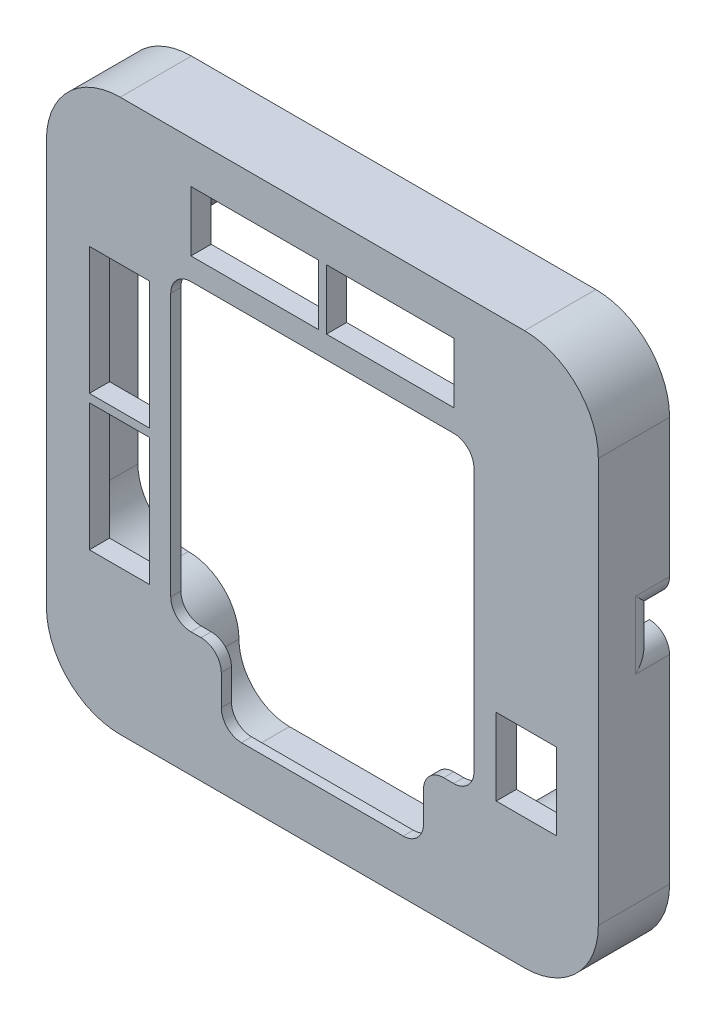
SolidWorks part; units mm, degrees
ref_plane "Front Plane" through (0, 0, 0) normal (0, 0, 1) x (1, 0, 0)
ref_plane "Top Plane" through (0, 0, 0) normal (0, 1, 0) x (1, 0, 0)
ref_plane "Right Plane" through (0, 0, 0) normal (1, 0, 0) x (0, 0, -1)
sketch "Front_Sketch" plane through (0, 0, 0) normal (0, 0, 1) x (1, 0, 0)
  line L0 (-5, 0) -> (-45, 0) construction
  line L1 (0, 45) -> (0, 5) construction
  line L2 (-45, 50) -> (-5, 50) construction
  line L3 (-50, 5) -> (-50, 45) construction
  line L4 (-47.95, 12.1) -> (-44.05, 12.1) construction
  line L5 (-43.55, 12.1) -> (-44.05, 12.1) construction
  line L6 (-43.05, 12.1) -> (-43.55, 12.1) construction
  line L7 (-43.05, 12.1) -> (-42.2, 12.1) construction
  line L8 (-42.2, 12.1) -> (-42.2, 14.05) construction
  line L9 (-42.2, 14.8) -> (-42.2, 14.05) construction
  line L10 (-42.2, 15.55) -> (-42.2, 14.8) construction
  line L11 (-42.2, 15.55) -> (-42.2, 21.05) construction
  line L12 (-42.2, 21.05) -> (-42.2, 21.8) construction
  line L13 (-42.2, 21.8) -> (-42.2, 22.55) construction
  line L14 (-42.2, 22.55) -> (-42.2, 24.5) construction
  line L15 (-42.2, 24.5) -> (-43.05, 24.5) construction
  line L16 (-43.55, 24.5) -> (-43.05, 24.5) construction
  line L17 (-43.55, 24.5) -> (-44.05, 24.5) construction
  line L18 (-47.95, 24.5) -> (-47.95, 12.1) construction
  line L19 (-44.05, 24.5) -> (-47.95, 24.5) construction
  line L20 (-47.95, 25.5) -> (-44.05, 25.5) construction
  line L21 (-43.55, 25.5) -> (-44.05, 25.5) construction
  line L22 (-43.05, 25.5) -> (-43.55, 25.5) construction
  line L23 (-43.05, 25.5) -> (-42.2, 25.5) construction
  line L24 (-42.2, 25.5) -> (-42.2, 27.45) construction
  line L25 (-42.2, 28.2) -> (-42.2, 27.45) construction
  line L26 (-42.2, 27.7) -> (-42.2, 27.45) construction
  line L27 (-42.2, 28.95) -> (-42.2, 28.2) construction
  line L28 (-42.2, 28.95) -> (-42.2, 34.45) construction
  line L29 (-42.2, 34.45) -> (-42.2, 35.2) construction
  line L30 (-42.2, 35.2) -> (-42.2, 35.95) construction
  line L31 (-42.2, 35.7) -> (-42.2, 35.95) construction
  line L32 (-42.2, 35.95) -> (-42.2, 37.9) construction
  line L33 (-42.2, 37.9) -> (-43.05, 37.9) construction
  line L34 (-43.55, 37.9) -> (-43.05, 37.9) construction
  line L35 (-43.55, 37.9) -> (-44.05, 37.9) construction
  line L36 (-44.05, 37.9) -> (-47.95, 37.9) construction
  line L37 (-47.95, 37.9) -> (-47.95, 25.5) construction
  line L38 (-34.45, 42.3) -> (-35.2, 42.3) construction
  line L39 (-35.2, 42.3) -> (-35.95, 42.3) construction
  line L40 (-35.7, 42.3) -> (-35.95, 42.3) construction
  line L41 (-37.9, 42.3) -> (-35.95, 42.3) construction
  line L42 (-37.9, 43.15) -> (-37.9, 42.3) construction
  line L43 (-37.9, 43.15) -> (-37.9, 43.65) construction
  line L44 (-37.9, 43.65) -> (-37.9, 44.15) construction
  line L45 (-34.45, 42.3) -> (-28.95, 42.3) construction
  line L46 (-28.95, 42.3) -> (-28.2, 42.3) construction
  line L47 (-28.2, 42.3) -> (-27.45, 42.3) construction
  line L48 (-27.7, 42.3) -> (-27.45, 42.3) construction
  line L49 (-27.45, 42.3) -> (-25.5, 42.3) construction
  line L50 (-25.5, 42.3) -> (-25.5, 43.15) construction
  line L51 (-25.5, 43.65) -> (-25.5, 43.15) construction
  line L52 (-25.5, 43.65) -> (-25.5, 44.15) construction
  line L53 (-25.5, 44.15) -> (-25.5, 48.05) construction
  line L54 (-25.5, 48.05) -> (-37.9, 48.05) construction
  line L55 (-37.9, 48.05) -> (-37.9, 44.15) construction
  line L56 (-24.5, 43.65) -> (-24.5, 44.15) construction
  line L57 (-24.5, 43.15) -> (-24.5, 43.65) construction
  line L58 (-24.5, 43.15) -> (-24.5, 42.3) construction
  line L59 (-24.5, 42.3) -> (-22.55, 42.3) construction
  line L60 (-21.8, 42.3) -> (-22.55, 42.3) construction
  line L61 (-21.05, 42.3) -> (-21.8, 42.3) construction
  line L62 (-21.05, 42.3) -> (-15.55, 42.3) construction
  line L63 (-15.55, 42.3) -> (-14.8, 42.3) construction
  line L64 (-14.8, 42.3) -> (-14.05, 42.3) construction
  line L65 (-14.3, 42.3) -> (-14.05, 42.3) construction
  line L66 (-14.05, 42.3) -> (-12.1, 42.3) construction
  line L67 (-12.1, 42.3) -> (-12.1, 43.15) construction
  line L68 (-12.1, 43.65) -> (-12.1, 43.15) construction
  line L69 (-12.1, 43.65) -> (-12.1, 44.15) construction
  line L70 (-12.1, 44.15) -> (-12.1, 48.05) construction
  line L71 (-12.1, 48.05) -> (-24.5, 48.05) construction
  line L72 (-24.5, 48.05) -> (-24.5, 44.15) construction
  line L73 (-6.35, 10.7) -> (-5.85, 10.7) construction
  line L74 (-6.35, 10.7) -> (-6.85, 10.7) construction
  line L75 (-7.7, 10.7) -> (-6.85, 10.7) construction
  line L76 (-7.7, 12.65) -> (-7.7, 10.7) construction
  line L77 (-7.7, 13.4) -> (-7.7, 12.65) construction
  line L78 (-7.7, 13.4) -> (-7.7, 15.4) construction
  line L79 (-7.7, 15.4) -> (-7.7, 16.15) construction
  line L80 (-7.7, 15.9) -> (-7.7, 16.15) construction
  line L81 (-7.7, 18.1) -> (-7.7, 16.15) construction
  line L82 (-6.85, 18.1) -> (-7.7, 18.1) construction
  line L83 (-6.85, 18.1) -> (-6.35, 18.1) construction
  line L84 (-6.35, 18.1) -> (-5.85, 18.1) construction
  line L85 (-1.95, 18.1) -> (-5.85, 18.1) construction
  line L86 (-1.95, 10.7) -> (-1.95, 18.1) construction
  line L87 (-5.85, 10.7) -> (-1.95, 10.7) construction
  line L88 (0.6, 26.77) -> (-0.4, 26.77) construction
  line L89 (0.6, 26.77) -> (0.8, 26.97) construction
  line L90 (0.8, 26.97) -> (0.8, 27.87) construction
  line L91 (0.8, 27.87) -> (0.6, 28.07) construction
  line L92 (0.6, 28.07) -> (-0.4, 28.07) construction
  line L93 (-5, 0) -> (-45, 0)
  line L94 (0, 45) -> (0, 5)
  line L95 (-45, 50) -> (-5, 50)
  line L96 (-50, 5) -> (-50, 45)
  line L97 (-47.95, 12.1) -> (-44.05, 12.1)
  line L98 (-43.55, 12.1) -> (-44.05, 12.1)
  line L99 (-43.05, 12.1) -> (-43.55, 12.1)
  line L100 (-43.05, 12.1) -> (-42.2, 12.1)
  line L101 (-42.2, 12.1) -> (-42.2, 14.05)
  line L102 (-42.2, 14.8) -> (-42.2, 14.05)
  line L103 (-42.2, 15.55) -> (-42.2, 14.8)
  line L104 (-42.2, 15.55) -> (-42.2, 21.05)
  line L105 (-42.2, 21.05) -> (-42.2, 21.8)
  line L106 (-42.2, 21.8) -> (-42.2, 22.55)
  line L107 (-42.2, 22.55) -> (-42.2, 24.5)
  line L108 (-42.2, 24.5) -> (-43.05, 24.5)
  line L109 (-43.55, 24.5) -> (-43.05, 24.5)
  line L110 (-43.55, 24.5) -> (-44.05, 24.5)
  line L111 (-47.95, 24.5) -> (-47.95, 12.1)
  line L112 (-44.05, 24.5) -> (-47.95, 24.5)
  line L113 (-47.95, 25.5) -> (-44.05, 25.5)
  line L114 (-43.55, 25.5) -> (-44.05, 25.5)
  line L115 (-43.05, 25.5) -> (-43.55, 25.5)
  line L116 (-43.05, 25.5) -> (-42.2, 25.5)
  line L117 (-42.2, 25.5) -> (-42.2, 27.45)
  line L118 (-42.2, 28.2) -> (-42.2, 27.45)
  line L119 (-42.2, 27.7) -> (-42.2, 27.45)
  line L120 (-42.2, 28.95) -> (-42.2, 28.2)
  line L121 (-42.2, 28.95) -> (-42.2, 34.45)
  line L122 (-42.2, 34.45) -> (-42.2, 35.2)
  line L123 (-42.2, 35.2) -> (-42.2, 35.95)
  line L124 (-42.2, 35.7) -> (-42.2, 35.95)
  line L125 (-42.2, 35.95) -> (-42.2, 37.9)
  line L126 (-42.2, 37.9) -> (-43.05, 37.9)
  line L127 (-43.55, 37.9) -> (-43.05, 37.9)
  line L128 (-43.55, 37.9) -> (-44.05, 37.9)
  line L129 (-44.05, 37.9) -> (-47.95, 37.9)
  line L130 (-47.95, 37.9) -> (-47.95, 25.5)
  line L131 (-34.45, 42.3) -> (-35.2, 42.3)
  line L132 (-35.2, 42.3) -> (-35.95, 42.3)
  line L133 (-35.7, 42.3) -> (-35.95, 42.3)
  line L134 (-37.9, 42.3) -> (-35.95, 42.3)
  line L135 (-37.9, 43.15) -> (-37.9, 42.3)
  line L136 (-37.9, 43.15) -> (-37.9, 43.65)
  line L137 (-37.9, 43.65) -> (-37.9, 44.15)
  line L138 (-34.45, 42.3) -> (-28.95, 42.3)
  line L139 (-28.95, 42.3) -> (-28.2, 42.3)
  line L140 (-28.2, 42.3) -> (-27.45, 42.3)
  line L141 (-27.7, 42.3) -> (-27.45, 42.3)
  line L142 (-27.45, 42.3) -> (-25.5, 42.3)
  line L143 (-25.5, 42.3) -> (-25.5, 43.15)
  line L144 (-25.5, 43.65) -> (-25.5, 43.15)
  line L145 (-25.5, 43.65) -> (-25.5, 44.15)
  line L146 (-25.5, 44.15) -> (-25.5, 48.05)
  line L147 (-25.5, 48.05) -> (-37.9, 48.05)
  line L148 (-37.9, 48.05) -> (-37.9, 44.15)
  line L149 (-24.5, 43.65) -> (-24.5, 44.15)
  line L150 (-24.5, 43.15) -> (-24.5, 43.65)
  line L151 (-24.5, 43.15) -> (-24.5, 42.3)
  line L152 (-24.5, 42.3) -> (-22.55, 42.3)
  line L153 (-21.8, 42.3) -> (-22.55, 42.3)
  line L154 (-21.05, 42.3) -> (-21.8, 42.3)
  line L155 (-21.05, 42.3) -> (-15.55, 42.3)
  line L156 (-15.55, 42.3) -> (-14.8, 42.3)
  line L157 (-14.8, 42.3) -> (-14.05, 42.3)
  line L158 (-14.3, 42.3) -> (-14.05, 42.3)
  line L159 (-14.05, 42.3) -> (-12.1, 42.3)
  line L160 (-12.1, 42.3) -> (-12.1, 43.15)
  line L161 (-12.1, 43.65) -> (-12.1, 43.15)
  line L162 (-12.1, 43.65) -> (-12.1, 44.15)
  line L163 (-12.1, 44.15) -> (-12.1, 48.05)
  line L164 (-12.1, 48.05) -> (-24.5, 48.05)
  line L165 (-24.5, 48.05) -> (-24.5, 44.15)
  line L166 (-6.35, 10.7) -> (-5.85, 10.7)
  line L167 (-6.35, 10.7) -> (-6.85, 10.7)
  line L168 (-7.7, 10.7) -> (-6.85, 10.7)
  line L169 (-7.7, 12.65) -> (-7.7, 10.7)
  line L170 (-7.7, 13.4) -> (-7.7, 12.65)
  line L171 (-7.7, 13.4) -> (-7.7, 15.4)
  line L172 (-7.7, 15.4) -> (-7.7, 16.15)
  line L173 (-7.7, 15.9) -> (-7.7, 16.15)
  line L174 (-7.7, 18.1) -> (-7.7, 16.15)
  line L175 (-6.85, 18.1) -> (-7.7, 18.1)
  line L176 (-6.85, 18.1) -> (-6.35, 18.1)
  line L177 (-6.35, 18.1) -> (-5.85, 18.1)
  line L178 (-1.95, 18.1) -> (-5.85, 18.1)
  line L179 (-1.95, 10.7) -> (-1.95, 18.1)
  line L180 (-5.85, 10.7) -> (-1.95, 10.7)
  line L181 (0.6, 26.77) -> (-0.4, 26.77)
  line L182 (0.6, 26.77) -> (0.8, 26.97)
  line L183 (0.8, 26.97) -> (0.8, 27.87)
  line L184 (0.8, 27.87) -> (0.6, 28.07)
  line L185 (0.6, 28.07) -> (-0.4, 28.07)
  arc A0 (-5, 0) -> (0, 5) centre (-5, 5) ccw construction
  arc A1 (-50, 5) -> (-45, 0) centre (-45, 5) ccw construction
  arc A2 (0, 45) -> (-5, 50) centre (-5, 45) ccw construction
  arc A3 (-45, 50) -> (-50, 45) centre (-45, 45) ccw construction
  circle A4 centre (-5, 5) radius 2.15 construction
  circle A5 centre (-45, 5) radius 2.15 construction
  circle A6 centre (-45, 45) radius 2.15 construction
  circle A7 centre (-5, 45) radius 2.15 construction
  arc A8 (-5, 0) -> (0, 5) centre (-5, 5) ccw
  arc A9 (-50, 5) -> (-45, 0) centre (-45, 5) ccw
  arc A10 (0, 45) -> (-5, 50) centre (-5, 45) ccw
  arc A11 (-45, 50) -> (-50, 45) centre (-45, 45) ccw
  circle A12 centre (-5, 5) radius 2.15
  circle A13 centre (-45, 5) radius 2.15
  circle A14 centre (-45, 45) radius 2.15
  circle A15 centre (-5, 45) radius 2.15
sketch "Top_Sketch" plane through (0, 0, 0) normal (0, 1, 0) x (1, 0, 0)
  line L0 (-12.1, -1.64) -> (-12.1, -8.64) construction
  line L1 (-24.5, -1.64) -> (-24.5, -8.64) construction
  line L2 (-12.1, -8.64) -> (-24.5, -8.64) construction
  line L3 (-25.5, -8.64) -> (-37.9, -8.64) construction
  line L4 (-25.5, -1.64) -> (-25.5, -8.64) construction
  line L5 (-37.9, -1.64) -> (-37.9, -8.64) construction
  line L6 (-42.2, -1.64) -> (-42.2, -8.64) construction
  line L7 (-43.05, -8.64) -> (-42.2, -8.64) construction
  line L8 (-47.95, -8.64) -> (-44.05, -8.64) construction
  line L9 (-47.95, -1.64) -> (-47.95, -8.64) construction
  line L10 (-7.7, -1.64) -> (-7.7, -8.64) construction
  line L11 (-7.7, -8.64) -> (-6.85, -8.64) construction
  line L12 (-5.85, -8.64) -> (-1.95, -8.64) construction
  line L13 (-1.95, -1.64) -> (-1.95, -8.64) construction
  line L14 (0.6, -2.84) -> (-0.4, -2.84) construction
  line L15 (0.6, -2.84) -> (0.8, -2.84) construction
  line L16 (0.8, -2.04) -> (0.8, -2.84) construction
  line L17 (0.6, -2.04) -> (0.8, -2.04) construction
  line L18 (0.6, -2.04) -> (-0.5, -2.04) construction
  line L19 (-5, -1.59) -> (0, -1.59) construction
  line L20 (0, 0) -> (0, -1.59) construction
  line L21 (-5, 0) -> (0, 0) construction
  line L22 (-5, -1.59) -> (-45, -1.59) construction
  line L23 (-45, 0) -> (-5, 0) construction
  line L24 (-50, -1.59) -> (-45, -1.59) construction
  line L25 (-50, 0) -> (-45, 0) construction
  line L26 (-50, 0) -> (-50, -1.59) construction
  line L27 (-12.1, -1.64) -> (-12.1, -8.64)
  line L28 (-24.5, -1.64) -> (-24.5, -8.64)
  line L29 (-12.1, -8.64) -> (-24.5, -8.64)
  line L30 (-25.5, -8.64) -> (-37.9, -8.64)
  line L31 (-25.5, -1.64) -> (-25.5, -8.64)
  line L32 (-37.9, -1.64) -> (-37.9, -8.64)
  line L33 (-42.2, -1.64) -> (-42.2, -8.64)
  line L34 (-43.05, -8.64) -> (-42.2, -8.64)
  line L35 (-47.95, -8.64) -> (-44.05, -8.64)
  line L36 (-47.95, -1.64) -> (-47.95, -8.64)
  line L37 (-7.7, -1.64) -> (-7.7, -8.64)
  line L38 (-7.7, -8.64) -> (-6.85, -8.64)
  line L39 (-5.85, -8.64) -> (-1.95, -8.64)
  line L40 (-1.95, -1.64) -> (-1.95, -8.64)
  line L41 (0.6, -2.84) -> (-0.4, -2.84)
  line L42 (0.6, -2.84) -> (0.8, -2.84)
  line L43 (0.8, -2.04) -> (0.8, -2.84)
  line L44 (0.6, -2.04) -> (0.8, -2.04)
  line L45 (0.6, -2.04) -> (-0.5, -2.04)
  line L46 (-5, -1.59) -> (0, -1.59)
  line L47 (0, 0) -> (0, -1.59)
  line L48 (-5, 0) -> (0, 0)
  line L49 (-5, -1.59) -> (-45, -1.59)
  line L50 (-45, 0) -> (-5, 0)
  line L51 (-50, -1.59) -> (-45, -1.59)
  line L52 (-50, 0) -> (-45, 0)
  line L53 (-50, 0) -> (-50, -1.59)
  point P4 (0, 0)
  point P5 (0, 0)
  point P9 (0, 0)
  point P11 (0, 0)
sketch "Right_Sketch" plane through (0, 0, 0) normal (1, 0, 0) x (0, 0, -1)
  line L0 (-1.64, 10.7) -> (-8.64, 10.7) construction
  line L1 (-8.64, 10.7) -> (-8.64, 18.1) construction
  line L2 (-8.64, 23.85) -> (-8.64, 12.75) construction
  line L3 (-8.64, 22.55) -> (-8.64, 24.5) construction
  line L4 (-1.64, 24.5) -> (-8.64, 24.5) construction
  line L5 (-1.64, 25.5) -> (-8.64, 25.5) construction
  line L6 (-8.64, 37.25) -> (-8.64, 26.15) construction
  line L7 (-8.64, 25.5) -> (-8.64, 27.45) construction
  line L8 (-8.64, 28.95) -> (-8.64, 34.45) construction
  line L9 (-8.64, 35.95) -> (-8.64, 37.9) construction
  line L10 (-1.64, 37.9) -> (-8.64, 37.9) construction
  line L11 (-8.64, 42.3) -> (-8.64, 43.15) construction
  line L12 (-1.64, 48.05) -> (-8.64, 48.05) construction
  line L13 (-8.64, 44.15) -> (-8.64, 48.05) construction
  line L14 (-1.64, 42.3) -> (-8.64, 42.3) construction
  line L15 (-2.44, 29.25) -> (-2.84, 29.25) construction
  line L16 (-2.04, 28.07) -> (-2.84, 28.07) construction
  line L17 (-2.84, 27.87) -> (-2.84, 28.07) construction
  line L18 (-2.84, 26.97) -> (-2.84, 27.87) construction
  line L19 (-2.84, 26.77) -> (-2.84, 26.97) construction
  line L20 (-2.04, 26.97) -> (-2.04, 27.87) construction
  line L21 (-2.04, 26.77) -> (-2.04, 26.97) construction
  line L22 (-2.04, 26.77) -> (-2.84, 26.77) construction
  line L23 (0, 50) -> (-1.59, 50) construction
  line L24 (0, 45) -> (0, 50) construction
  line L25 (-1.59, 50) -> (-1.59, 45) construction
  line L26 (0, 5) -> (0, 45) construction
  line L27 (-1.59, 45) -> (-1.59, 5) construction
  line L28 (0, 5) -> (0, 0) construction
  line L29 (-1.59, 5) -> (-1.59, 0) construction
  line L30 (0, 0) -> (-1.59, 0) construction
  line L31 (-1.64, 10.7) -> (-8.64, 10.7)
  line L32 (-8.64, 10.7) -> (-8.64, 18.1)
  line L33 (-8.64, 23.85) -> (-8.64, 12.75)
  line L34 (-8.64, 22.55) -> (-8.64, 24.5)
  line L35 (-1.64, 24.5) -> (-8.64, 24.5)
  line L36 (-1.64, 25.5) -> (-8.64, 25.5)
  line L37 (-8.64, 37.25) -> (-8.64, 26.15)
  line L38 (-8.64, 25.5) -> (-8.64, 27.45)
  line L39 (-8.64, 28.95) -> (-8.64, 34.45)
  line L40 (-8.64, 35.95) -> (-8.64, 37.9)
  line L41 (-1.64, 37.9) -> (-8.64, 37.9)
  line L42 (-8.64, 42.3) -> (-8.64, 43.15)
  line L43 (-1.64, 48.05) -> (-8.64, 48.05)
  line L44 (-8.64, 44.15) -> (-8.64, 48.05)
  line L45 (-1.64, 42.3) -> (-8.64, 42.3)
  line L46 (-2.44, 29.25) -> (-2.84, 29.25)
  line L47 (-2.04, 28.07) -> (-2.84, 28.07)
  line L48 (-2.84, 27.87) -> (-2.84, 28.07)
  line L49 (-2.84, 26.97) -> (-2.84, 27.87)
  line L50 (-2.84, 26.77) -> (-2.84, 26.97)
  line L51 (-2.04, 26.97) -> (-2.04, 27.87)
  line L52 (-2.04, 26.77) -> (-2.04, 26.97)
  line L53 (-2.04, 26.77) -> (-2.84, 26.77)
  line L54 (0, 50) -> (-1.59, 50)
  line L55 (0, 45) -> (0, 50)
  line L56 (-1.59, 50) -> (-1.59, 45)
  line L57 (0, 5) -> (0, 45)
  line L58 (-1.59, 45) -> (-1.59, 5)
  line L59 (0, 5) -> (0, 0)
  line L60 (-1.59, 5) -> (-1.59, 0)
  line L61 (0, 0) -> (-1.59, 0)
sketch "Wall_Sketch" plane through (0, 0, 0) normal (0, 0, 1) x (1, 0, 0)
  line L4 (-52.3, 45) -> (-52.3, 5)
  line L5 (-45, -2.3) -> (-5, -2.3)
  line L6 (2.3, 5) -> (2.3, 45)
  line L7 (-5, 52.3) -> (-45, 52.3)
  line L8 (-5, 50.3) -> (-45, 50.3)
  line L9 (0.3, 5) -> (0.3, 45)
  line L10 (-45, -0.3) -> (-5, -0.3)
  line L11 (-50.3, 45) -> (-50.3, 5)
  line L12 (-5, 50.3) -> (-45, 50.3)
  line L13 (0.3, 5) -> (0.3, 45)
  line L14 (-45, -0.3) -> (-5, -0.3)
  line L15 (-50.3, 45) -> (-50.3, 5)
  arc A4 (-45, 52.3) -> (-52.3, 45) centre (-45, 45) ccw
  arc A5 (-52.3, 5) -> (-45, -2.3) centre (-45, 5) ccw
  arc A6 (-5, -2.3) -> (2.3, 5) centre (-5, 5) ccw
  arc A7 (2.3, 45) -> (-5, 52.3) centre (-5, 45) ccw
  arc A8 (0.3, 45) -> (-5, 50.3) centre (-5, 45) ccw
  arc A9 (-5, -0.3) -> (0.3, 5) centre (-5, 5) ccw
  arc A10 (-50.3, 5) -> (-45, -0.3) centre (-45, 5) ccw
  arc A11 (-45, 50.3) -> (-50.3, 45) centre (-45, 45) ccw
  arc A12 (0.3, 45) -> (-5, 50.3) centre (-5, 45) ccw
  arc A13 (-5, -0.3) -> (0.3, 5) centre (-5, 5) ccw
  arc A14 (-50.3, 5) -> (-45, -0.3) centre (-45, 5) ccw
  arc A15 (-45, 50.3) -> (-50.3, 45) centre (-45, 45) ccw
  dimension "D1" = 0.3
  dimension "D2" = 2
extrude "Wall_Extrude_Boss" add sketch "Wall_Sketch" against normal up to vertex (-1.59 mm away) from vertex up to point (-50, 0, 1.59) starting at point (-42.2, 0, 8.64)
sketch "Ceiling_Sketch" plane through (0, 0, 8.64) normal (0, 0, 1) x (1, 0, 0)
  line L0 (-45, -0.3) -> (-5, -0.3) construction
  line L1 (0.3, 5) -> (0.3, 45) construction
  line L2 (-5, 50.3) -> (-45, 50.3) construction
  line L3 (-50.3, 45) -> (-50.3, 5) construction
  line L4 (-45, -0.3) -> (-5, -0.3)
  line L5 (0.3, 5) -> (0.3, 45)
  line L6 (-5, 50.3) -> (-45, 50.3)
  line L7 (-50.3, 45) -> (-50.3, 5)
  arc A0 (-50.3, 5) -> (-45, -0.3) centre (-45, 5) ccw construction
  arc A1 (-5, -0.3) -> (0.3, 5) centre (-5, 5) ccw construction
  arc A2 (0.3, 45) -> (-5, 50.3) centre (-5, 45) ccw construction
  arc A3 (-45, 50.3) -> (-50.3, 45) centre (-45, 45) ccw construction
  arc A4 (-50.3, 5) -> (-45, -0.3) centre (-45, 5) ccw
  arc A5 (-5, -0.3) -> (0.3, 5) centre (-5, 5) ccw
  arc A6 (0.3, 45) -> (-5, 50.3) centre (-5, 45) ccw
  arc A7 (-45, 50.3) -> (-50.3, 45) centre (-45, 45) ccw
extrude "Ceiling_Extrude_Boss" add sketch "Ceiling_Sketch" against normal blind 2
sketch "Screws_Blocks_Sketch" plane through (0, 0, 6.64) normal (0, 0, -1) x (-1, 0, 0)
  line L0 (45, -0.3) -> (5, -0.3) construction
  line L7 (9.7, -0.3) -> (4.7, -0.3)
  line L8 (9.7, -0.3) -> (9.7, 9.7)
  line L9 (9.7, 9.7) -> (-0.3, 9.7)
  line L10 (-0.3, 4.7) -> (-0.3, 9.7)
  line L11 (5, 50.3) -> (45, 50.3) construction
  line L12 (9.7, 50.3) -> (4.7, 50.3)
  line L13 (9.7, 50.3) -> (9.7, 40.3)
  line L14 (9.7, 40.3) -> (-0.3, 40.3)
  line L15 (-0.3, 45.3) -> (-0.3, 40.3)
  line L16 (-0.3, 5) -> (-0.3, 45) construction
  line L22 (50.3, 45) -> (50.3, 5) construction
  line L23 (40.3, 50.3) -> (45.3, 50.3)
  line L24 (40.3, 50.3) -> (40.3, 40.3)
  line L25 (40.3, 40.3) -> (50.3, 40.3)
  line L26 (50.3, 45.3) -> (50.3, 40.3)
  line L27 (45, -0.3) -> (5, -0.3) construction
  line L28 (40.3, -0.3) -> (45.3, -0.3)
  line L29 (40.3, -0.3) -> (40.3, 9.7)
  line L30 (40.3, 9.7) -> (50.3, 9.7)
  line L31 (50.3, 4.7) -> (50.3, 9.7)
  arc A0 (4.7, 50.3) -> (-0.3, 45.3) centre (4.7, 45.3) ccw
  arc A1 (4.7, -0.3) -> (-0.3, 4.7) centre (4.7, 4.7) cw
  arc A2 (45.3, -0.3) -> (50.3, 4.7) centre (45.3, 4.7) ccw
  arc A3 (45.3, 50.3) -> (50.3, 45.3) centre (45.3, 45.3) cw
  point P12 (-0.3, 11.7)
  point P28 (0, 11.7)
  dimension "D3" = 5
  dimension "D1" = 10
  dimension "D2" = 10
extrude "Screws_Blocks_Extrude_Boss" add sketch "Screws_Blocks_Sketch" along normal up to vertex (5.05 mm away) up to point (-50, 0, 1.59)
fillet "Screws_Blocks_Fillet" radius 5 12 edges at (-40.3, 50.3, 4.115) (-50.3, 40.3, 4.115) (-40.3, 40.3, 4.115) (-9.7, 50.3, 4.115) (-9.7, 40.3, 4.115) (0.3, 40.3, 4.115) (0.3, 9.7, 4.115) (-9.7, 9.7, 4.115) (-9.7, -0.3, 4.115) (-40.3, -0.3, 4.115) (-40.3, 9.7, 4.115) (-50.3, 9.7, 4.115)
sketch "Nuts_Sketch" plane through (0, 0, 1.59) normal (0, 0, -1) x (-1, 0, 0)
  line L1 (1.5, 44.9959) -> (3.2536, 41.9668)
  line L2 (3.2536, 41.9668) -> (6.7536, 41.971)
  line L3 (6.7536, 41.971) -> (8.5, 45.0041)
  line L4 (8.5, 45.0041) -> (6.7464, 48.0332)
  line L5 (6.7464, 48.0332) -> (3.2464, 48.029)
  line L6 (3.2464, 48.029) -> (1.5, 44.9959)
  line L7 (41.5, 45) -> (43.25, 41.9689)
  line L8 (43.25, 41.9689) -> (46.75, 41.9689)
  line L9 (46.75, 41.9689) -> (48.5, 45)
  line L10 (48.5, 45) -> (46.75, 48.0311)
  line L11 (46.75, 48.0311) -> (43.25, 48.0311)
  line L12 (43.25, 48.0311) -> (41.5, 45)
  line L13 (41.5, 5) -> (43.25, 1.9689)
  line L14 (43.25, 1.9689) -> (46.75, 1.9689)
  line L15 (46.75, 1.9689) -> (48.5, 5)
  line L16 (48.5, 5) -> (46.75, 8.0311)
  line L17 (46.75, 8.0311) -> (43.25, 8.0311)
  line L18 (43.25, 8.0311) -> (41.5, 5)
  line L19 (8.5, 4.9882) -> (6.7602, 8.0252)
  line L20 (6.7602, 8.0252) -> (3.2602, 8.0369)
  line L21 (3.2602, 8.0369) -> (1.5, 5.0118)
  line L22 (1.5, 5.0118) -> (3.2398, 1.9748)
  line L23 (3.2398, 1.9748) -> (6.7398, 1.9631)
  line L24 (6.7398, 1.9631) -> (8.5, 4.9882)
  circle A0 centre (5, 45) radius 3.0311 construction
  circle A1 centre (45, 45) radius 3.0311 construction
  circle A2 centre (45, 5) radius 3.0311 construction
  circle A3 centre (5, 5) radius 3.0311 construction
  dimension "D1" = 7
extrude "Nuts_Extrude" cut sketch "Nuts_Sketch" against normal blind 3.2
sketch "Screws_Sketch" plane through (0, 0, 4.79) normal (0, 0, -1) x (-1, 0, 0)
  circle A0 centre (5, 45) radius 2.15
  circle A1 centre (45, 45) radius 2.15
  circle A2 centre (45, 5) radius 2.15
  circle A3 centre (5, 5) radius 2.15
extrude "Screws_Hooles_Extrude" cut sketch "Screws_Sketch" against normal blind 2.5
sketch "Connectors_Sketch" plane through (0, 0, 8.64) normal (0, 0, 1) x (1, 0, 0)
  line L0 (-25.5, 48.05) -> (-37.9, 48.05) construction
  line L1 (-38, 48.15) -> (-25.4, 48.15)
  line L2 (-38, 48.15) -> (-38, 42.2)
  line L3 (-38, 42.2) -> (-25.4, 42.2)
  line L4 (-25.4, 48.15) -> (-25.4, 42.2)
  line L5 (-37.9, 43.15) -> (-37.9, 42.3) construction
  line L6 (-37.9, 42.3) -> (-35.95, 42.3) construction
  line L7 (-25.5, 44.15) -> (-25.5, 48.05) construction
  line L8 (-24.5, 48.05) -> (-24.5, 44.15) construction
  line L9 (-24.6, 48.15) -> (-12, 48.15)
  line L10 (-24.6, 48.15) -> (-24.6, 42.2)
  line L11 (-24.6, 42.2) -> (-12, 42.2)
  line L12 (-12, 48.15) -> (-12, 42.2)
  line L13 (-48.05, 25.4) -> (-42.1, 25.4)
  line L14 (-48.05, 25.4) -> (-48.05, 38)
  line L15 (-48.05, 38) -> (-42.1, 38)
  line L16 (-42.1, 25.4) -> (-42.1, 38)
  line L17 (-48.05, 24.6) -> (-42.1, 24.6)
  line L18 (-48.05, 24.6) -> (-48.05, 12)
  line L19 (-48.05, 12) -> (-42.1, 12)
  line L20 (-42.1, 24.6) -> (-42.1, 12)
  line L21 (-7.8, 18.2) -> (-1.85, 18.2)
  line L22 (-7.8, 18.2) -> (-7.8, 10.6)
  line L23 (-7.8, 10.6) -> (-1.85, 10.6)
  line L24 (-1.85, 18.2) -> (-1.85, 10.6)
  line L25 (-12.1, 48.05) -> (-24.5, 48.05) construction
  line L26 (-24.5, 42.3) -> (-22.55, 42.3) construction
  line L27 (-12.1, 44.15) -> (-12.1, 48.05) construction
  line L28 (-47.95, 25.5) -> (-44.05, 25.5) construction
  line L29 (-47.95, 37.9) -> (-47.95, 25.5) construction
  line L30 (-42.2, 25.5) -> (-42.2, 27.45) construction
  line L31 (-44.05, 37.9) -> (-47.95, 37.9) construction
  line L32 (-44.05, 24.5) -> (-47.95, 24.5) construction
  line L33 (-47.95, 24.5) -> (-47.95, 12.1) construction
  line L34 (-42.2, 22.55) -> (-42.2, 24.5) construction
  line L35 (-47.95, 12.1) -> (-44.05, 12.1) construction
  line L36 (-1.95, 18.1) -> (-5.85, 18.1) construction
  line L37 (-7.7, 18.1) -> (-7.7, 16.15) construction
  line L38 (-1.95, 10.7) -> (-1.95, 18.1) construction
  line L39 (-7.7, 10.7) -> (-6.85, 10.7) construction
  dimension "D1" = 0.1
  dimension "D2" = 0.1
  dimension "D3" = 0.1
  dimension "D4" = 0.1
  dimension "D5" = 0.1
  dimension "D6" = 0.1
  dimension "D7" = 0.1
  dimension "D8" = 0.1
  dimension "D9" = 0.1
  dimension "D10" = 0.1
  dimension "D11" = 0.1
  dimension "D12" = 0.1
  dimension "D13" = 0.1
  dimension "D14" = 0.1
  dimension "D15" = 0.1
  dimension "D16" = 0.1
  dimension "D17" = 0.1
  dimension "D18" = 0.1
  dimension "D19" = 0.1
  dimension "D20" = 0.1
extrude "Connectors_Extrude" cut sketch "Connectors_Sketch" against normal blind 2.5
sketch "Switch_Sketch" plane through (2.3, 0, 0) normal (1, 0, 0) x (0, 0, -1)
  line L0 (-2.04, 26.77) -> (-2.84, 26.77) construction
  line L1 (-1.54, 26.67) -> (-2.94, 26.67)
  line L2 (-1.54, 26.67) -> (-1.54, 29.35)
  line L3 (-1.54, 29.35) -> (-2.94, 29.35)
  line L4 (-2.94, 26.67) -> (-2.94, 29.35)
  line L5 (-2.44, 29.25) -> (-2.84, 29.25) construction
  line L6 (-2.04, 26.97) -> (-2.04, 27.87) construction
  line L7 (-2.84, 26.97) -> (-2.84, 27.87) construction
  dimension "D1" = 0.1
  dimension "D2" = 0.1
  dimension "D3" = 0.5
  dimension "D4" = 0.1
extrude "Switch_Extrude" cut sketch "Switch_Sketch" against normal blind 2.5
fillet "Switch_Fillet" radius 2 3 edges at (2.3, 28.01, 2.94) (2.3, 29.35, 2.265) (2.3, 26.67, 2.265)
sketch "Glass_Sketch" plane through (0, 0, 6.64) normal (0, 0, -1) x (-1, 0, 0)
  line L0 (50, 25) -> (0, 25) construction
  line L1 (50, 5) -> (50, 45) construction
  line L2 (25, 50) -> (25, 0) construction
  line L3 (45, 50) -> (5, 50) construction
  line L4 (5, 0) -> (45, 0) construction
  line L5 (0, 45) -> (0, 5) construction
  line L6 (35, 8) -> (35, 5)
  line L7 (12, 10) -> (13, 10)
  line L8 (10, 12) -> (10, 38)
  line L9 (12, 40) -> (38, 40)
  line L10 (40, 12) -> (40, 38)
  line L11 (10, 10) -> (40, 40) construction
  line L12 (10, 40) -> (40, 10) construction
  line L13 (33, 3) -> (17, 3)
  line L14 (15, 5) -> (15, 8)
  line L15 (37, 10) -> (38, 10)
  arc A0 (38, 10) -> (40, 12) centre (38, 12) ccw
  arc A1 (12, 10) -> (10, 12) centre (12, 12) cw
  arc A2 (38, 40) -> (40, 38) centre (38, 38) cw
  arc A3 (10, 38) -> (12, 40) centre (12, 38) cw
  arc A4 (15, 8) -> (13, 10) centre (13, 8) ccw
  arc A5 (17, 3) -> (15, 5) centre (17, 5) cw
  arc A6 (35, 5) -> (33, 3) centre (33, 5) cw
  arc A7 (35, 8) -> (37, 10) centre (37, 8) cw
  point P16 (25, 25)
  point P37 (15, 3)
  point P40 (35, 3)
  point P43 (35, 10)
  point P44 (12.5, 10)
  dimension "D5" = 2
  dimension "D1" = 30
  dimension "D2" = 30
  dimension "D3" = 5
  dimension "D4" = 20
  dimension "D6" = 7
extrude "Glass_Extrude" cut sketch "Glass_Sketch" against normal blind 2.5
sketch "Glass_Fit_Sketch" plane through (0, 0, 6.64) normal (0, 0, -1) x (-1, 0, 0)
  line L16 (37, 8.5) -> (38, 8.5)
  line L17 (36.5, 5) -> (36.5, 8)
  line L18 (17, 1.5) -> (33, 1.5)
  line L19 (13.5, 8) -> (13.5, 5)
  line L20 (12, 8.5) -> (13, 8.5)
  line L21 (8.5, 38) -> (8.5, 12)
  line L22 (41.5, 12) -> (41.5, 38)
  line L23 (38, 41.5) -> (12, 41.5)
  line L24 (37, 8.5) -> (38, 8.5)
  line L25 (36.5, 5) -> (36.5, 8)
  line L26 (17, 1.5) -> (33, 1.5)
  line L27 (13.5, 8) -> (13.5, 5)
  line L28 (12, 8.5) -> (13, 8.5)
  line L29 (8.5, 38) -> (8.5, 12)
  line L30 (41.5, 12) -> (41.5, 38)
  line L31 (38, 41.5) -> (12, 41.5)
  arc A16 (38, 8.5) -> (41.5, 12) centre (38, 12) ccw
  arc A17 (37, 8.5) -> (36.5, 8) centre (37, 8) ccw
  arc A18 (33, 1.5) -> (36.5, 5) centre (33, 5) ccw
  arc A19 (13.5, 5) -> (17, 1.5) centre (17, 5) ccw
  arc A20 (13.5, 8) -> (13, 8.5) centre (13, 8) ccw
  arc A21 (8.5, 12) -> (12, 8.5) centre (12, 12) ccw
  arc A22 (12, 41.5) -> (8.5, 38) centre (12, 38) ccw
  arc A23 (41.5, 38) -> (38, 41.5) centre (38, 38) ccw
  arc A24 (38, 8.5) -> (41.5, 12) centre (38, 12) ccw
  arc A25 (37, 8.5) -> (36.5, 8) centre (37, 8) ccw
  arc A26 (33, 1.5) -> (36.5, 5) centre (33, 5) ccw
  arc A27 (13.5, 5) -> (17, 1.5) centre (17, 5) ccw
  arc A28 (13.5, 8) -> (13, 8.5) centre (13, 8) ccw
  arc A29 (8.5, 12) -> (12, 8.5) centre (12, 12) ccw
  arc A30 (12, 41.5) -> (8.5, 38) centre (12, 38) ccw
  arc A31 (41.5, 38) -> (38, 41.5) centre (38, 38) ccw
  dimension "D1" = 1.5
extrude "Glass_Fit_Extrude" cut sketch "Glass_Fit_Sketch" against normal blind 1
